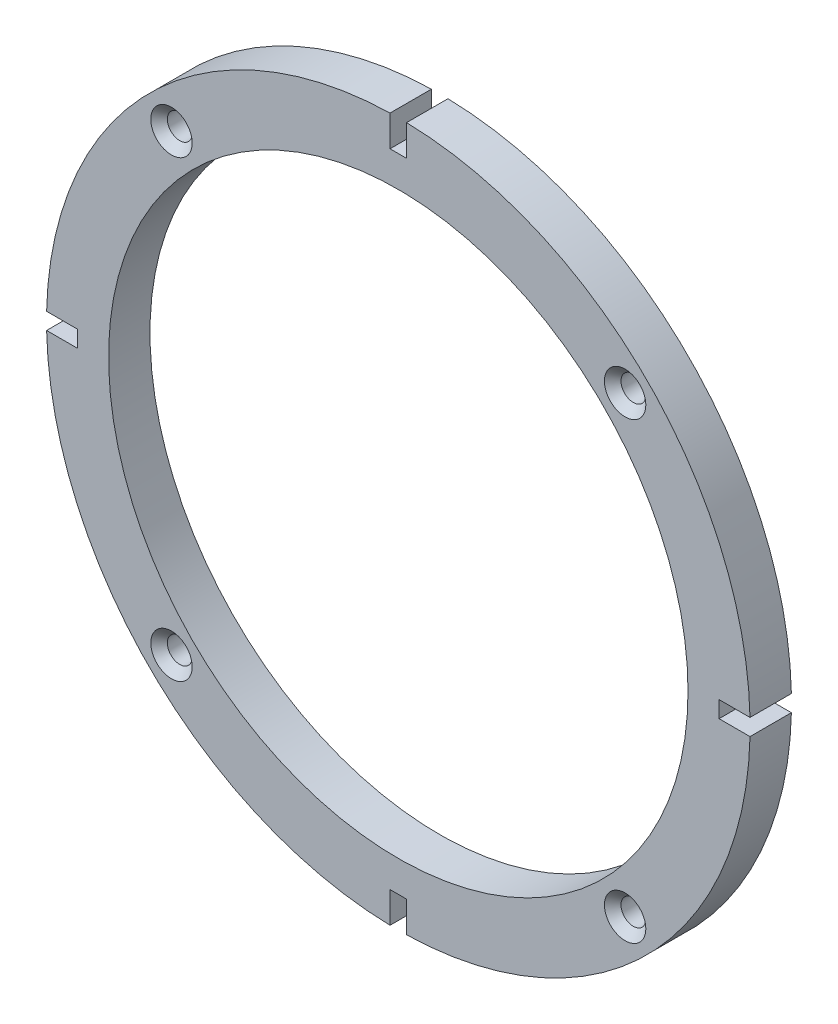
SolidWorks part; units mm, degrees
material "Stop 1060"
ref_plane "Płaszczyzna przednia" through (0, 0, 0) normal (0, 0, 1) x (1, 0, 0)
ref_plane "Płaszczyzna górna" through (0, 0, 0) normal (0, 1, 0) x (1, 0, 0)
ref_plane "Płaszczyzna prawa" through (0, 0, 0) normal (1, 0, 0) x (0, 0, -1)
sketch "Sketch1" plane through (0, 0, 0) normal (0, 0, 1) x (1, 0, 0)
  line L0 (84.9765, -2) -> (77.4996, -2)
  line L1 (-2, 77.4996) -> (2, 77.4996)
  line L2 (-2, 77.4996) -> (-2, 84.9765)
  line L4 (2, 84.9765) -> (2, 77.4996)
  line L5 (77.4996, 2) -> (84.9765, 2)
  line L6 (77.4996, 2) -> (77.4996, -2)
  line L7 (-2, -84.9765) -> (-2, -77.4996)
  line L8 (2, -77.4996) -> (2, -84.9765)
  line L9 (2, -77.4996) -> (-2, -77.4996)
  line L10 (-84.9765, 2) -> (-77.4996, 2)
  line L11 (-77.4996, -2) -> (-84.9765, -2)
  line L12 (-77.4996, -2) -> (-77.4996, 2)
  circle A0 centre (0, 0) radius 70
  arc A1 (-2, 84.9765) -> (-84.9765, 2) centre (0, 0) ccw
  arc A2 (-84.9765, -2) -> (-2, -84.9765) centre (0, 0) ccw
  arc A3 (2, -84.9765) -> (84.9765, -2) centre (0, 0) ccw
  arc A4 (84.9765, 2) -> (2, 84.9765) centre (0, 0) ccw
  point P6 (-2, 77.4996)
  point P7 (2, 77.4996)
  point P24 (0, 0)
  dimension "D1" = 170
  dimension "D2" = 140
  dimension "D3" = 77.4996
  dimension "D4" = 2
  dimension "D5" = 4
  dimension "D6" = 4
extrude "Boss-Extrude1" add sketch "Sketch1" along normal blind 10 contours A0 | A1 L10 L12 L11 A2 L7 L9 L8 A3 L0 L6 L5 A4 L4 L1 L2 region at (0, 0, 0)
sketch "Sketch2" plane through (0, 0, 0) normal (0, 0, -1) x (-1, 0, 0)
  line L0 (0, 0) -> (-73.6832, 73.6832) construction
  line L1 (0, 0) -> (0, 118.1493) construction
  circle A0 centre (-54.8008, 54.8008) radius 3
  arc A1 (-2, 84.9765) -> (-84.9765, 2) centre (0, 0) ccw construction
  circle A2 centre (54.8008, 54.8008) radius 3
  circle A3 centre (54.8008, -54.8008) radius 3
  circle A4 centre (-54.8008, -54.8008) radius 3
  point P18 (0, 0)
  dimension "D3" = 6
  dimension "D1" = 77.5
  dimension "D2" = 45
  dimension "D4" = 4
extrude "Wytnij-wyciągnięcie1" cut sketch "Sketch2" against normal blind 10
sketch "Szkic1" plane through (0, 0, 0) normal (0, 0, -1) x (-1, 0, 0)
  circle A0 centre (-54.8008, 54.8008) radius 5
  dimension "D1" = 10
extrude "Wytnij-wyciągnięcie2" cut sketch "Szkic1" against normal blind 2 contours A0
pattern_circular "Szyk kołowy1" count 4 over 360 about axis through (0, 0, 10) along (0, 0, -1) of "Wytnij-wyciągnięcie2"
chamfer "Sfazowanie1" distance 2 4 edges at (51.8008, -54.8008, 10) (51.8008, 54.8008, 10) (-57.8008, 54.8008, 10) (-57.8008, -54.8008, 10)
